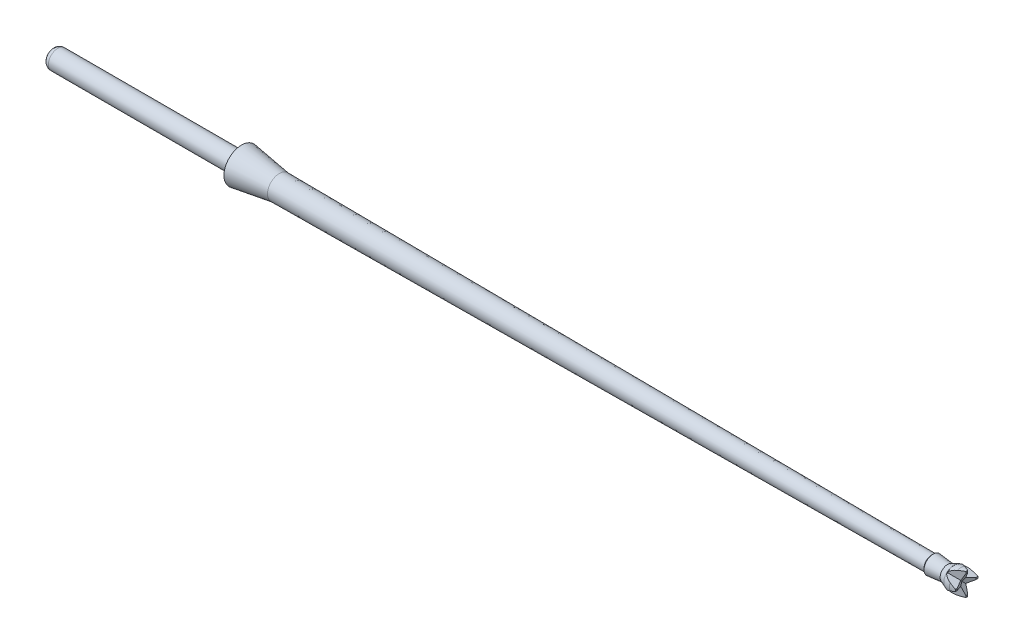
SolidWorks part; units mm, degrees
ref_plane "Front Plane" through (0, 0, 0) normal (0, 0, 1) x (1, 0, 0)
ref_plane "Top Plane" through (0, 0, 0) normal (0, 1, 0) x (1, 0, 0)
ref_plane "Right Plane" through (0, 0, 0) normal (1, 0, 0) x (0, 0, -1)
sketch "Sketch1" plane through (0, 0, 0) normal (0, 0, 1) x (1, 0, 0)
  line L0 (0, 1) -> (0, 1.85)
  line L1 (0, 0) -> (-20, 0)
  line L2 (0, 0) -> (0, 1) construction
  line L3 (0, 1) -> (-20, 1)
  line L4 (-20, 0) -> (-20, 1)
  line L5 (0, 1.85) -> (4, 1.25)
  line L6 (4, 1.25) -> (72.9, 0.8)
  line L7 (72.9, 0.8) -> (73.05, 0.95)
  line L8 (73.05, 0.95) -> (74.6, 0.8)
  line L9 (74.6, 0.8) -> (75.6, 1.2)
  line L10 (75.6, 1.2) -> (76.6, 1.2)
  line L11 (76.6, 1.2) -> (76.6, 0)
  line L12 (76.6, 0) -> (0, 0)
  dimension "D1" = 20
  dimension "D2" = 1
  dimension "D3" = 1.85
  dimension "D4" = 4
  dimension "D5" = 1.25
  dimension "D6" = 72.9
  dimension "D7" = 0.8
  dimension "D8" = 0.95
  dimension "D9" = 1.7
  dimension "D10" = 45
  dimension "D11" = 0.8
  dimension "D12" = 1.2
  dimension "D13" = 2
  dimension "D14" = 1
  dimension "D15" = 76.6
revolve "Revolve1" add sketch "Sketch1" angle 360 about L12
fillet "Fillet1" radius 2 1 edges at (75.6, 0, -1.2)
sketch "Sketch2" plane through (0, 0, 0) normal (0, 0, 1) x (1, 0, 0)
  line L0 (0, 0) -> (76.6, 0) construction
  line L1 (76.6, -1.2) -> (76.6, 1.2) construction
  line L2 (76.6, 0.1) -> (75.3, 0.697)
  line L3 (75.3, 0.697) -> (75.3, 1.3)
  line L4 (75.3, 1.3) -> (76.6, 1.3)
  line L5 (76.6, 1.3) -> (76.6, 0.1)
  dimension "D1" = 0.1
  dimension "D2" = 0.697
  dimension "D3" = 1.3
  dimension "D4" = 1.3
extrude "Cut-Extrude1" cut sketch "Sketch2" against normal through all both and the other way through all
mirror "Mirror1" about plane through (0, 0, 0) normal (0, 1, 0) of "Cut-Extrude1"
sketch "Sketch3" plane through (0, 0, 0) normal (0, 1, 0) x (1, 0, 0)
  line L0 (0, 0) -> (76.6, 0) construction
  line L1 (76.6, 1.1958) -> (76.6, -1.1958) construction
  line L2 (76.6, 1) -> (76.6, -1)
  line L3 (76.6, 1) -> (76.1, 0)
  line L4 (76.1, 0) -> (76.6, -1)
  dimension "D1" = 1
  dimension "D2" = 1
  dimension "D3" = 0.5
extrude "Cut-Extrude2" cut sketch "Sketch3" against normal through all both and the other way through all
ref_plane "Plane1" through (74.6, 0, 0) normal (1, 0, 0) x (0, 0, -1)
split "Split1" trim tools "Plane1" bodies to split 104 resulting bodies 105 106
move or copy body "Body-Move/Copy1" bodies to move or copy 105 copy yes number of copies 1 rotation origin (0, 0, -0.0154) rotation axis (1, 0, 0) rotation angle 90
combine bodies "Combine1" operation type add bodies to combine 106 107 105
fillet "Fillet2" radius 0.6 1 edges at (-20, 0, -1)
